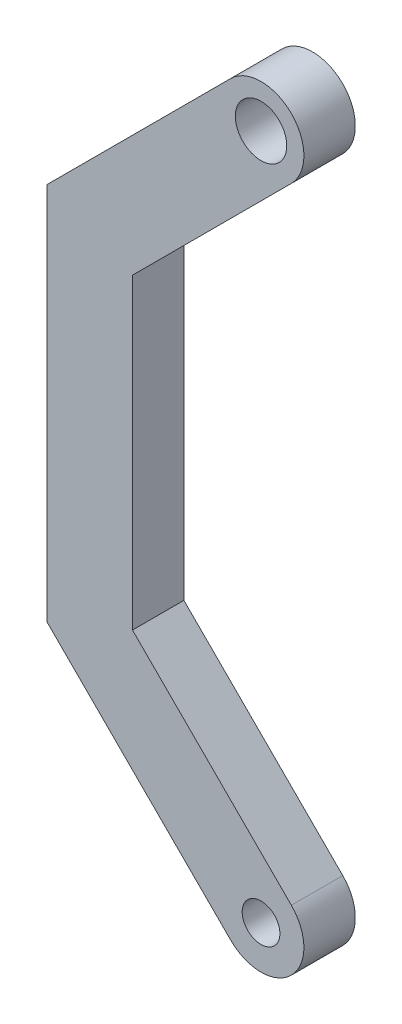
SolidWorks part; units mm, degrees
ref_plane "Alzado" through (0, 0, 0) normal (0, 0, 1) x (1, 0, 0)
ref_plane "Planta" through (0, 0, 0) normal (0, 1, 0) x (1, 0, 0)
ref_plane "Vista lateral" through (0, 0, 0) normal (1, 0, 0) x (0, 0, -1)
sketch "Croquis1" plane through (0, 0, 0) normal (0, 0, 1) x (1, 0, 0)
  line L0 (0, 0) -> (0, 40) construction
  line L1 (0, 0) -> (-10, 10) construction
  line L2 (-10, 10) -> (-10, 30) construction
  line L3 (-10, 30) -> (0, 40) construction
  line L4 (1.7678, 1.7678) -> (-7.5, 11.0355)
  line L5 (-7.5, 11.0355) -> (-7.5, 28.9645)
  line L6 (-7.5, 28.9645) -> (1.7678, 38.2322)
  line L7 (-1.7678, -1.7678) -> (-12.5, 8.9645)
  line L8 (-12.5, 8.9645) -> (-12.5, 31.0355)
  line L9 (-12.5, 31.0355) -> (-1.7678, 41.7678)
  circle A0 centre (0, 0) radius 1.1
  circle A1 centre (0, 0) radius 2.5
  circle A4 centre (0, 40) radius 1.5
  circle A5 centre (0, 40) radius 2.5
  dimension "D1" = 2.2
  dimension "D2" = 5
  dimension "D3" = 3
  dimension "D4" = 5
  dimension "D5" = 40
  dimension "D6" = 45
  dimension "D7" = 45
  dimension "D8" = 20
  dimension "D9" = 2.5
  dimension "D10" = 2.5
extrude "Saliente-Extruir1" add sketch "Croquis1" along normal blind 3 contours A5 L9 L8 L7 A1 L4 L5 L6 | A5 A4 | A1 A0 region at (-7.7028, 20, 0) region at (2.2444, 0.9296, 0) region at (-1.7178, 38.2822, 0)
